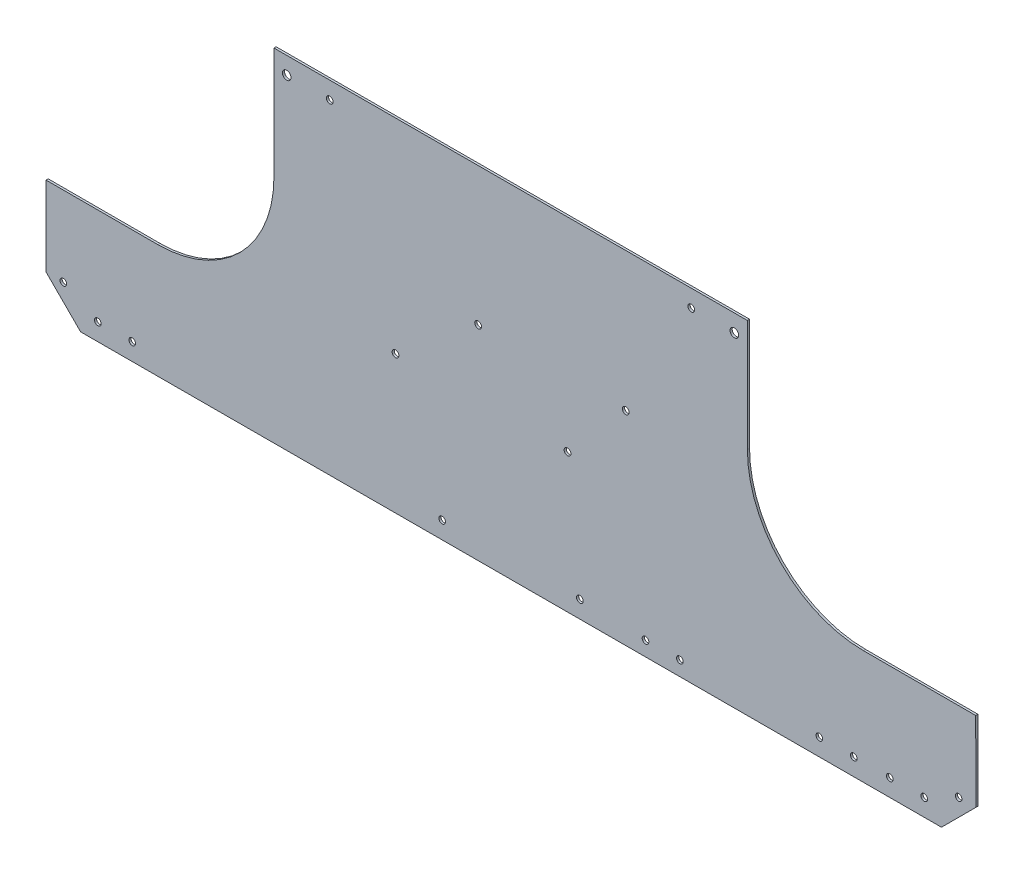
SolidWorks part; units mm, degrees
material "Perspex (TM) GS Acrylic Cast Sheet"
ref_plane "Front Plane" through (0, 0, 0) normal (0, 0, 1) x (1, 0, 0)
ref_plane "Top Plane" through (0, 0, 0) normal (0, 1, 0) x (1, 0, 0)
ref_plane "Right Plane" through (0, 0, 0) normal (1, 0, 0) x (0, 0, -1)
sketch "Sketch1" plane through (0, 0, 0) normal (0, 0, 1) x (1, 0, 0)
  line L1 (-457.2, -304.8) -> (457.2, -304.8)
  line L2 (-457.2, -304.8) -> (-457.2, 304.8)
  line L3 (-457.2, 304.8) -> (457.2, 304.8)
  line L4 (457.2, -304.8) -> (457.2, 304.8)
  line L5 (0, 304.8) -> (0, -304.8) construction
  line L6 (-457.2, 0) -> (457.2, 0) construction
  point P0 (0, 0)
  point P4 (-320.04, 0)
  point P5 (320.04, 0)
  point P6 (0, 213.36)
  point P7 (0, -213.36)
  dimension "Length" = 914.4
  dimension "Width" = 609.6
  dimension "Break" = 137.16
  dimension "D2" = 137.16
  dimension "D1" = 91.44
  dimension "D3" = 91.44
sketch "Sketch2" plane through (0, 0, 0) normal (1, 0, 0) x (0, 0, -1)
  line L0 (-0.7938, -304.8) -> (0.7938, -304.8)
  dimension "Thickness" = 1.5875
sketch "Sketch3" plane through (0, 0, 0) normal (0, 0, 1) x (1, 0, 0)
  line L0 (-457.2, -304.8) -> (-457.2, 304.8) construction
  line L1 (-457.2, -304.8) -> (457.2, -304.8) construction
  line L2 (457.2, -304.8) -> (457.2, 304.8) construction
  line L3 (-457.2, 304.8) -> (457.2, 304.8) construction
  line L4 (-457.2, -304.8) -> (-457.2, 304.8)
  line L5 (-457.2, -304.8) -> (457.2, -304.8)
  line L6 (457.2, -304.8) -> (457.2, 304.8)
  line L7 (-457.2, 304.8) -> (457.2, 304.8)
extrude "Boss-Extrude1" add sketch "Sketch3" along normal mid plane 1.5875
sketch "Sketch4" plane through (0, 0, 0.7937) normal (0, 0, 1) x (1, 0, 0)
  line L1 (-362.5066, 0.4474) -> (318.2125, 1.5649)
  line L2 (-339.2322, -251.9272) -> (-364.674, -226.4854)
  line L5 (-363.9625, -659.9558) -> (-365.0466, 0.4433) construction
  line L12 (-364.674, -226.4854) -> (-365.0424, -2.0967)
  line L15 (-339.2322, -251.9272) -> (295.7669, -250.8848)
  line L26 (295.7669, -250.8848) -> (321.1253, -225.5264)
  line L27 (320.7942, -23.8309) -> (321.8783, -684.23) construction
  line L28 (321.1253, -225.5264) -> (320.7567, -0.9709)
  arc A2 (318.2125, 1.5649) -> (320.7567, -0.9709) centre (318.2167, -0.9751) cw
  arc A3 (-362.5066, 0.4474) -> (-365.0424, -2.0967) centre (-362.5024, -2.0926) ccw
  point P12 (320.7525, 1.5691)
  point P15 (-365.0466, 0.4433)
  dimension "D1" = 2.54
  dimension "D2" = 2.54
extrude "Cut-Extrude1" cut sketch "Sketch4" against normal blind 2.54 flip side to cut
sketch "Sketch12" plane through (0, 0, -0.7937) normal (0, 0, -1) x (-1, 0, 0)
  line L19 (196.6362, 20.4048) -> (384.7638, 20.0959)
  line L20 (384.4556, -167.696) -> (384.7638, 20.0959)
  line L21 (282.2232, -167.696) -> (384.4556, -167.696)
  line L22 (196.6362, -81.8669) -> (196.6362, 20.4048)
  arc A3 (282.2232, -167.696) -> (196.6362, -81.8669) centre (282.4657, -81.8669) cw
sketch "Sketch9" plane through (0, 0, 0.7937) normal (0, 0, 1) x (1, 0, 0)
  point P0 (-365.5467, -279.4147)
  point P1 (-339.7911, -292.1147)
  point P3 (-314.3911, -292.1147)
  point P5 (-365.5467, -229.8463)
  point P15 (270.1645, -292.1147)
  point P17 (295.5645, -292.1147)
  point P19 (321.3201, -279.4147)
  point P21 (320.9651, -229.8463)
  point P23 (-219.4967, -52.0463)
  point P25 (174.9151, -52.0463)
hole_wizard "#10 (0.1935) Diameter Hole1" positions "Sketch10" profile "Sketch11" hole size "#10" standard "ANSI Inch" end condition through all
sketch "Sketch10" plane through (0, 0, 0.7937) normal (0, 0, 1) x (1, 0, 0)
  point P55 (-301.1531, -239.1647)
  point P58 (-326.5531, -239.2064)
  point P61 (-351.9739, -226.5481)
  point P64 (-72.5534, -238.7894)
  point P67 (29.0464, -238.6226)
  point P70 (77.4365, -240.4866)
  point P73 (102.8365, -240.4449)
  point P76 (205.7032, -238.3326)
  point P79 (231.1032, -238.2909)
  point P82 (257.6461, -238.2474)
  point P85 (283.0461, -238.2057)
  point P88 (308.4252, -225.464)
  point P91 (-155.476, -11.9127)
  point P94 (111.2237, -11.4749)
sketch "Sketch11" plane through (-301.1531, -239.1647, 0.7937) normal (1, 0, 0) x (0, -1, 0)
  line L0 (0, 0) -> (0, 1.5875)
  line L1 (0, 1.5875) -> (2.4574, 1.5875)
  line L2 (2.4574, 1.5875) -> (2.4574, 0)
  line L5 (2.4574, 0) -> (0, 0)
  line L11 (0, -6.35) -> (0, 107.95) construction
  dimension "Thru Hole Dia." = 4.9149
  dimension "Thru Hole Depth" = 1.5875
sketch "Sketch13" plane through (0, 0, -0.7937) normal (0, 0, -1) x (-1, 0, 0)
  line L10 (-152.6132, -81.2206) -> (-152.6132, 23.5181)
  line L11 (-152.6132, 23.5181) -> (-342.941, 23.8305)
  line L12 (-343.254, -166.8413) -> (-342.941, 23.8305)
  line L13 (-238.2339, -166.8413) -> (-343.254, -166.8413)
  arc A3 (-238.2339, -166.8413) -> (-152.6132, -81.2206) centre (-238.2339, -81.2206) ccw
extrude "Cut-Extrude5" cut sketch "Sketch13" against normal blind 2.54
extrude "Cut-Extrude6" cut sketch "Sketch12" against normal blind 2.54
hole_wizard "1/4 (0.25) Diameter Hole1" positions "Sketch14" profile "Sketch15" hole size "1/4" standard "ANSI Inch" end condition through all
sketch "Sketch14" plane through (0, 0, -0.7937) normal (0, 0, -1) x (-1, 0, 0)
  point P0 (-142.9736, -11.4228)
  point P3 (187.2259, -11.9648)
sketch "Sketch15" plane through (142.9736, -11.4228, -0.7937) normal (1, 0, 0) x (0, 1, 0)
  line L0 (0, 0) -> (0, 1.5875)
  line L1 (0, 1.5875) -> (3.175, 1.5875)
  line L2 (3.175, 1.5875) -> (3.175, 0)
  line L5 (3.175, 0) -> (0, 0)
  line L11 (0, -6.35) -> (0, 107.95) construction
  dimension "Thru Hole Dia." = 6.35
  dimension "Thru Hole Depth" = 1.5875
hole_wizard "#10 Clearance Hole1" positions "Sketch16" profile "Sketch17" hole size "#10" standard "ANSI Inch" end condition through all
sketch "Sketch16" plane through (0, 0, -0.7937) normal (0, 0, -1) x (-1, 0, 0)
  point P0 (-62.8852, -101.187)
  point P2 (-19.9172, -149.0072)
  point P4 (46.0272, -100.8173)
  point P6 (106.9738, -149.7616)
sketch "Sketch17" plane through (62.8852, -101.187, -0.7937) normal (1, 0, 0) x (0, 1, 0)
  line L0 (0, 0) -> (0, 1.5875)
  line L1 (0, 1.5875) -> (2.4892, 1.5875)
  line L2 (2.4892, 1.5875) -> (2.4892, 0)
  line L5 (2.4892, 0) -> (0, 0)
  line L11 (0, -6.35) -> (0, 107.95) construction
  dimension "Thru Hole Dia." = 4.9784
  dimension "Thru Hole Depth" = 1.5875
equation "\"D1@Boss-Extrude1\"=\"thickness@sketch2\""
equation "\"Break@Sketch1\" = \"Length@Sketch1\" * 0.15"
equation "\"D2@Sketch1\" = \"Break@Sketch1\""
equation "\"D1@Sketch1\"=\"Width@Sketch1\"*0.15"
equation "\"D3@Sketch1\"=\"D1@Sketch1\""
